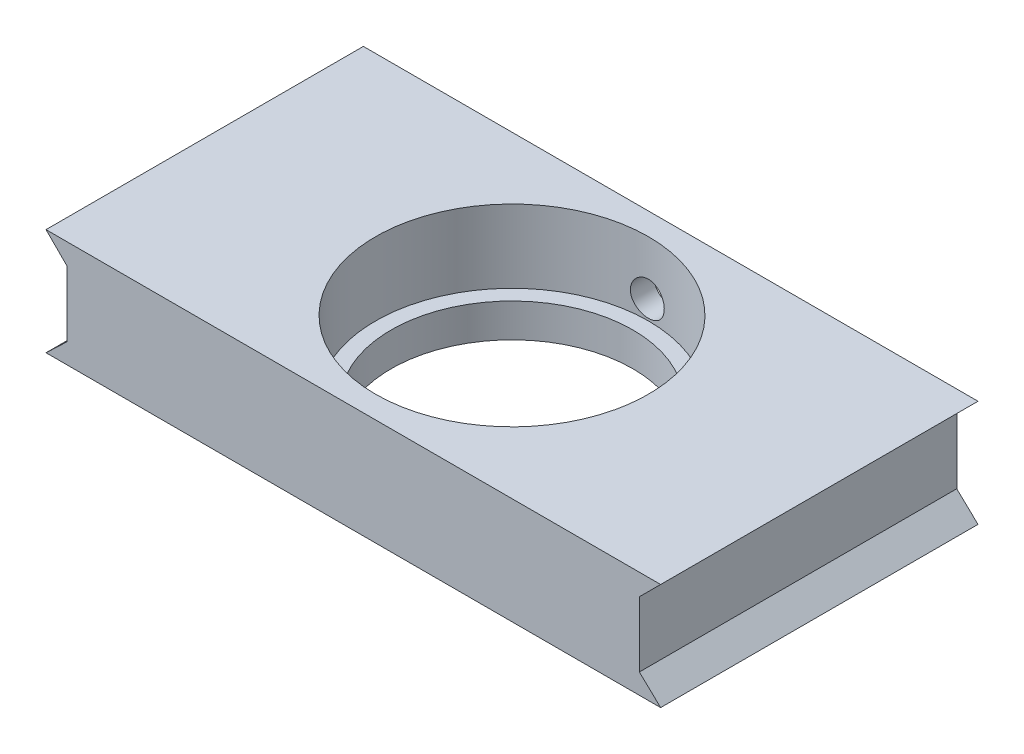
SolidWorks part; units mm, degrees
ref_plane "前视基准面" through (0, 0, 0) normal (0, 0, 1) x (1, 0, 0)
ref_plane "上视基准面" through (0, 0, 0) normal (0, 1, 0) x (1, 0, 0)
ref_plane "右视基准面" through (0, 0, 0) normal (1, 0, 0) x (0, 0, -1)
sketch "草图1" plane through (0, 0, 0) normal (0, 0, 1) x (1, 0, 0)
  line L0 (-26.485, 7.516) -> (-24.4768, 5.5078)
  line L1 (-26.485, 7.516) -> (31.615, 7.516)
  line L2 (-26.485, 7.516) -> (-26.485, -2.564)
  line L3 (-26.485, -2.564) -> (31.615, -2.564)
  line L4 (31.615, 7.516) -> (31.615, -2.564)
  line L5 (-24.4768, 5.5078) -> (-24.4768, -0.6522)
  line L6 (-24.4768, -0.6522) -> (-26.485, -2.564)
  line L7 (31.615, 7.516) -> (29.6068, 5.5078)
  line L8 (29.6068, 5.5078) -> (29.6068, -0.6522)
  line L9 (29.6068, -0.6522) -> (31.615, -2.564)
  dimension "D1" = 58.1
  dimension "D2" = 10.08
  dimension "D3" = 2.84
  dimension "D4" = 6.16
extrude "凸台-拉伸1" add sketch "草图1" along normal blind 30 contours L9 L8 L7 L1 L0 L5 L6 L3 region at (2.565, 2.4773, 0)
sketch "草图2" plane through (0, 7.516, 0) normal (0, 1, 0) x (1, 0, 0)
  line L0 (31.615, -30) -> (31.615, 0) construction
  circle A0 centre (2.565, -15) radius 12.9
  circle A1 centre (2.565, -15) radius 11.43
  dimension "D1" = 29.05
extrude "切除-拉伸1" cut sketch "草图2" against normal through all contours A1
extrude "切除-拉伸2" cut sketch "草图2<3>" against normal blind 6.9
sketch "草图2<3>" plane through (0, 7.516, 0) normal (0, 1, 0) x (1, 0, 0) same geometry as "草图2"
sketch "草图3" plane through (0, 0, 0) normal (0, 0, -1) x (-1, 0, 0)
  line L0 (-29.6068, 5.5078) -> (-29.6068, -0.6522) construction
  circle A0 centre (-2.5568, 2.4278) radius 1.6
  dimension "D1" = 27.05
extrude "切除-拉伸3" cut sketch "草图3" against normal blind 5
